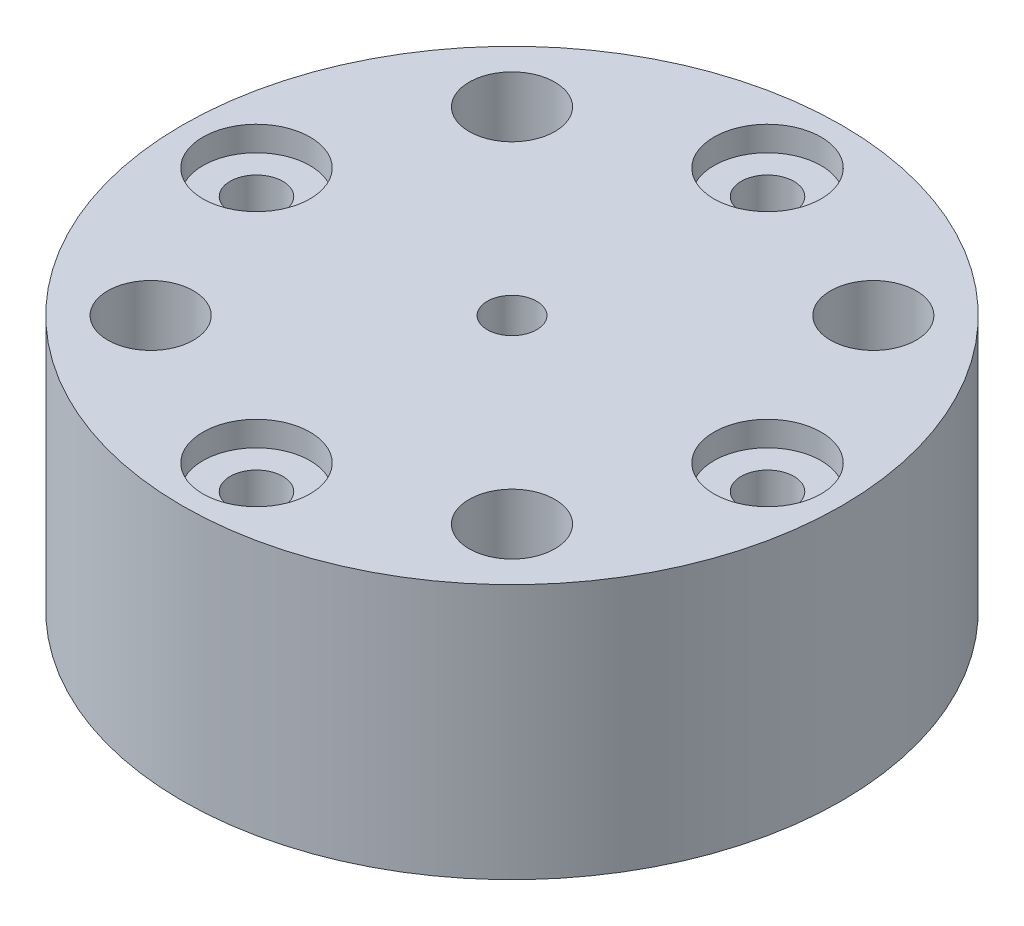
SolidWorks part; units mm, degrees
ref_plane "Front Plane" through (0, 0, 0) normal (0, 0, 1) x (1, 0, 0)
ref_plane "Top Plane" through (0, 0, 0) normal (0, 1, 0) x (1, 0, 0)
ref_plane "Right Plane" through (0, 0, 0) normal (1, 0, 0) x (0, 0, -1)
sketch "Sketch1" plane through (0, 0, 0) normal (0, 1, 0) x (1, 0, 0)
  circle A0 centre (0, 0) radius 15.5 construction
  circle A1 centre (0, 15.5) radius 1.6
  circle A2 centre (15.5, 0) radius 1.6
  circle A3 centre (0, -15.5) radius 1.6
  circle A4 centre (-15.5, 0) radius 1.6
  circle A5 centre (0, 0) radius 20
  circle A6 centre (0, 0) radius 4 construction
  circle A9 centre (0, 0) radius 1.5
  point P14 (0, 0)
  dimension "D1" = 31
  dimension "D2" = 3.2
  dimension "D4" = 40
  dimension "D5" = 8
  dimension "D7" = 3
  dimension "D3" = 4
extrude "Boss-Extrude1" add sketch "Sketch1" along normal blind 15.5
sketch "Sketch2" plane through (0, 15.5, 0) normal (0, 1, 0) x (1, 0, 0)
  circle A0 centre (0, 0) radius 15.5 construction
  circle A1 centre (0, 15.5) radius 3.25
  circle A2 centre (15.5, 0) radius 3.25
  circle A3 centre (0, -15.5) radius 3.25
  circle A4 centre (-15.5, 0) radius 3.25
  point P15 (0, 0)
  dimension "D1" = 6.5
  dimension "D2" = 4
extrude "Cut-Extrude1" cut sketch "Sketch2" against normal blind 1.5
sketch "Sketch3" plane through (0, 15.5, 0) normal (0, 1, 0) x (1, 0, 0)
  line L0 (-10.9602, 10.9602) -> (0, 0) construction
  line L1 (0, 0) -> (7.4736, 0) construction
  circle A0 centre (0, 0) radius 15.5 construction
  circle A1 centre (-10.9602, 10.9602) radius 2.6
  circle A2 centre (10.9602, 10.9602) radius 2.6
  circle A3 centre (10.9602, -10.9602) radius 2.6
  circle A4 centre (-10.9602, -10.9602) radius 2.6
  point P16 (0, 0)
  dimension "D1" = 5.2
  dimension "D2" = 135
  dimension "D3" = 4
extrude "Cut-Extrude2" cut sketch "Sketch3" against normal blind 10
